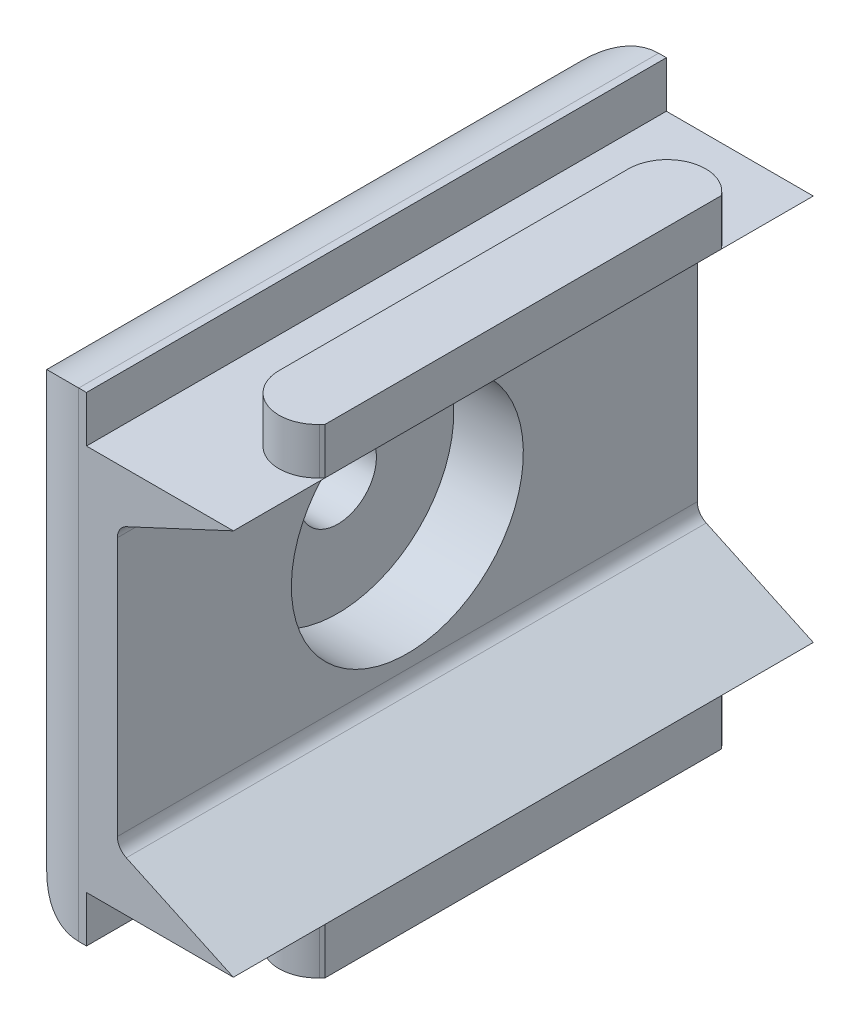
SolidWorks part; units mm, degrees
ref_plane "Front Plane" through (0, 0, 0) normal (0, 0, 1) x (1, 0, 0)
ref_plane "Top Plane" through (0, 0, 0) normal (0, 1, 0) x (1, 0, 0)
ref_plane "Right Plane" through (0, 0, 0) normal (1, 0, 0) x (0, 0, -1)
sketch "Sketch1" plane through (0, 0, 0) normal (0, 0, 1) x (1, 0, 0)
  line L0 (0, 0) -> (0, 50)
  line L6 (0, 25) -> (49.9015, 25) construction
  line L11 (30, 50) -> (15, 43.0054)
  line L12 (15, 43.0054) -> (15, 6.9946)
  line L13 (15, 6.9946) -> (30, 0)
  line L14 (0, 50) -> (30, 50)
  line L15 (0, 0) -> (30, 0)
  dimension "D1" = 50
extrude "Boss-Extrude1" add sketch "Sketch1" along normal blind 75
sketch "Sketch2" plane through (0, 0, 0) normal (-1, 0, 0) x (0, 0, 1)
  line L0 (0, 25) -> (75, 25) construction
  line L1 (0, 50) -> (0, 0) construction
  line L2 (75, 50) -> (75, 0) construction
  circle A0 centre (37.5, 25) radius 5
extrude "Cut-Extrude1" cut sketch "Sketch2" against normal through all contours A0
sketch "Sketch3" plane through (15, 0, 0) normal (1, 0, 0) x (0, 0, -1)
  circle A0 centre (-37.5, 25) radius 15
  dimension "D1" = 30
extrude "Cut-Extrude2" cut sketch "Sketch3" against normal blind 9
sketch "Sketch4" plane through (0, 50, 0) normal (0, 1, 0) x (1, 0, 0)
  line L0 (0, -75) -> (0, 0) construction
  line L1 (0, -37.5) -> (30, -37.5) construction
  line L2 (30, -75) -> (30, 0) construction
  line L3 (21, -37.5) -> (21, -2.295)
  line L4 (21, -37.5) -> (21, -72.705)
  line L5 (21, -2.295) -> (30, -11.8589)
  line L6 (30, -63.1411) -> (21, -72.705)
  line L11 (30, 0) -> (0, 0)
  line L12 (0, 0) -> (0, -75)
  line L13 (0, -75) -> (30, -75)
  line L14 (30, -75) -> (30, 0)
  line L18 (30, -63.1411) -> (30, -11.8589)
  point P8 (21, -19.8975)
  dimension "D1" = 21
  dimension "D2" = 35.205
  dimension "D3" = 35.205
  dimension "D4" = 43.26
  dimension "D5" = 43.26
  dimension "D6" = 0
extrude "Boss-Extrude2" add sketch "Sketch4" along normal blind 6
fillet "Fillet1" radius 5 2 edges at (21, 53, 2.295) (21, 53, 72.705)
sketch "Sketch5" plane through (0, 0, 0) normal (0, -1, 0) x (1, 0, 0)
  line L0 (21, 14.9043) -> (21, 60.0957) construction
  line L1 (30, 11.8589) -> (29.6413, 11.4777) construction
  line L2 (29.6413, 63.5223) -> (30, 63.1411) construction
  line L3 (21, 14.9043) -> (21, 60.0957)
  line L4 (0, 0) -> (30, 0)
  line L5 (30, 0) -> (30, 75)
  line L6 (30, 75) -> (0, 75)
  line L7 (0, 75) -> (0, 0)
  line L8 (0, 0) -> (30, 0)
  line L9 (30, 0) -> (30, 75)
  line L10 (30, 75) -> (0, 75)
  line L11 (0, 75) -> (0, 0)
  line L12 (30, 11.8589) -> (29.6413, 11.4777)
  line L13 (29.6413, 63.5223) -> (30, 63.1411)
  line L14 (30, 63.1411) -> (30, 11.8589)
  arc A0 (29.6413, 63.5223) -> (21, 60.0957) centre (26, 60.0957) ccw construction
  arc A1 (21, 14.9043) -> (29.6413, 11.4777) centre (26, 14.9043) ccw construction
  arc A2 (29.6413, 63.5223) -> (21, 60.0957) centre (26, 60.0957) ccw
  arc A3 (21, 14.9043) -> (29.6413, 11.4777) centre (26, 14.9043) ccw
  dimension "D1" = 0
extrude "Boss-Extrude3" add sketch "Sketch5" along normal blind 6 contours L3 A3 L12 L9 L13 A2 region at (25.5401, 0, 37.5)
sketch "Sketch6" plane through (0, 50, 0) normal (0, 1, 0) x (1, 0, 0)
  line L0 (30, 0) -> (0, 0) construction
  line L1 (0, -75) -> (11, -75)
  line L2 (0, -75) -> (0, 0)
  line L3 (0, 0) -> (11, 0)
  line L4 (11, -75) -> (11, 0)
  dimension "D1" = 11
extrude "Boss-Extrude4" add sketch "Sketch6" along normal blind 6
sketch "Sketch7" plane through (0, 0, 0) normal (0, -1, 0) x (1, 0, 0)
  line L0 (0, 75) -> (30, 75) construction
  line L1 (0, 0) -> (11, 0)
  line L2 (0, 0) -> (0, 75)
  line L3 (0, 75) -> (11, 75)
  line L4 (11, 0) -> (11, 75)
  dimension "D1" = 11
extrude "Boss-Extrude5" add sketch "Sketch7" along normal blind 6
fillet "Fillet2" radius 10 4 edges at (0, 56, 37.5) (0, 25, 75) (0, 25, 0) (0, -6, 37.5)
fillet "Fillet6" radius 2 2 edges at (15, 6.9946, 37.5) (15, 43.0054, 37.5)
equation "\"D3@Sketch4\"=\"D2@Sketch4\""
